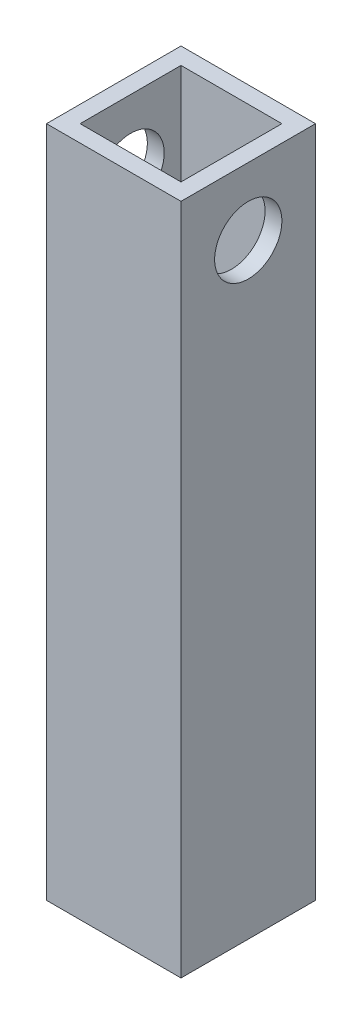
SolidWorks part; units mm, degrees
material "1060 Alloy"
ref_plane "Front Plane" through (0, 0, 0) normal (0, 0, 1) x (1, 0, 0)
ref_plane "Top Plane" through (0, 0, 0) normal (0, 1, 0) x (1, 0, 0)
ref_plane "Right Plane" through (0, 0, 0) normal (1, 0, 0) x (0, 0, -1)
sketch "Sketch1" plane through (0, 0, 0) normal (0, 1, 0) x (1, 0, 0)
  line L1 (-12.7, -12.7) -> (12.7, -12.7)
  line L2 (-12.7, -12.7) -> (-12.7, 12.7)
  line L3 (-12.7, 12.7) -> (12.7, 12.7)
  line L4 (12.7, -12.7) -> (12.7, 12.7)
  line L5 (-12.7, -12.7) -> (12.7, 12.7) construction
  line L6 (-12.7, 12.7) -> (12.7, -12.7) construction
  point P0 (0, 0)
  dimension "D1" = 25.4
extrude "Extrude-Thin1" add sketch "Sketch1" along normal blind 127 thin thin type one direction reverse wall 3.175
sketch "Sketch2" plane through (12.7, 0, 0) normal (1, 0, 0) x (0, 0, -1)
  line L0 (-12.7, 127) -> (12.7, 127) construction
  circle A0 centre (0, 114.3) radius 6.35
  point P5 (0, 127)
  dimension "D1" = 12.7
  dimension "D2" = 12.7
extrude "Cut-Extrude1" cut sketch "Sketch2" against normal through all
sketch "Sketch3" [suppressed] plane through (0, 0, -12.7) normal (0, 0, -1) x (-1, 0, 0)
  line L0 (-12.7, 0) -> (12.7, 0) construction
  circle A0 centre (0, 12.7) radius 6.35
  dimension "D1" = 12.7
  dimension "D2" = 12.7
extrude "Cut-Extrude2" [suppressed] cut sketch "Sketch3" against normal through all
